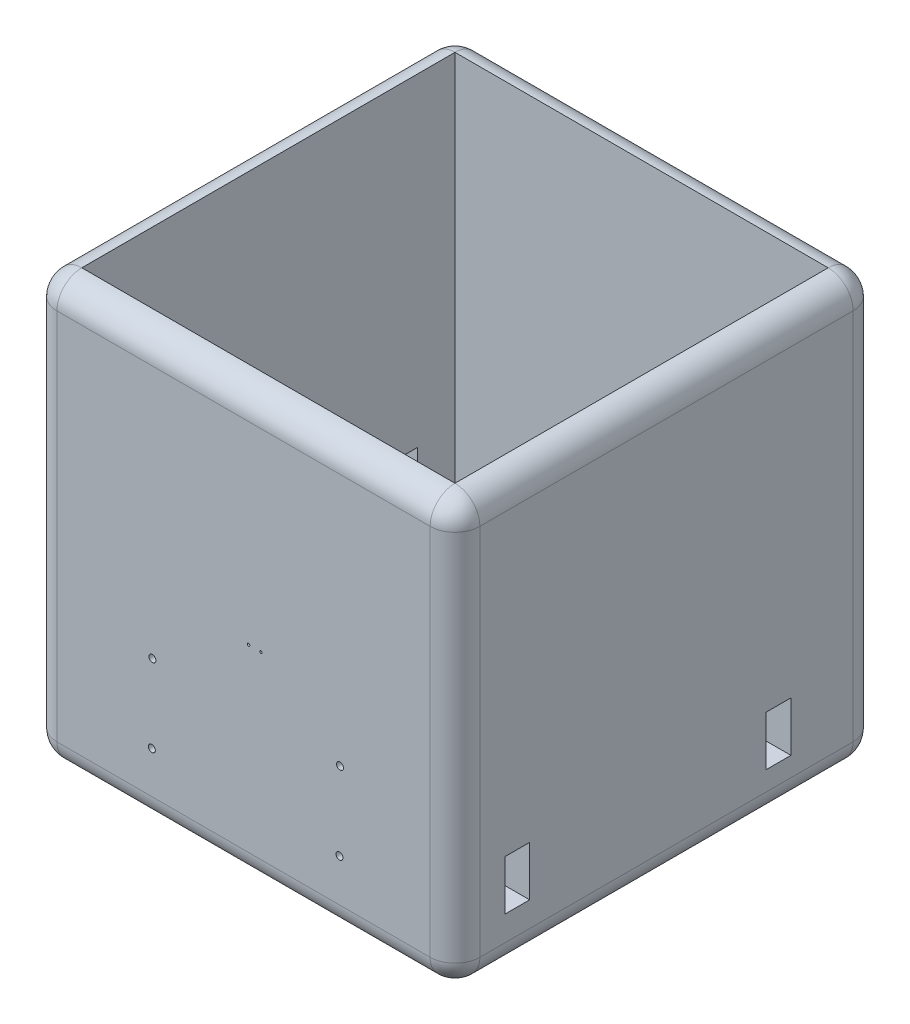
SolidWorks part; units mm, degrees
ref_plane "Front Plane" through (0, 0, 0) normal (0, 0, 1) x (1, 0, 0)
ref_plane "Top Plane" through (0, 0, 0) normal (0, 1, 0) x (1, 0, 0)
ref_plane "Right Plane" through (0, 0, 0) normal (1, 0, 0) x (0, 0, -1)
sketch "Sketch1" plane through (0, 0, 0) normal (0, 0, 1) x (1, 0, 0)
  line L5 (0, 170) -> (170, 170)
  line L6 (0, 170) -> (0, 0)
  line L7 (0, 0) -> (170, 0)
  line L8 (170, 170) -> (170, 0)
  dimension "D1" = 170
sketch "Sketch5" plane through (0, 0, 0) normal (0, 0, 1) x (1, 0, 0)
extrude "Boss-Extrude2" add sketch "Sketch1" along normal blind 170
fillet "Fillet5" radius 10 12 edges at (170, 170, 85) (85, 170, 0) (0, 85, 0) (170, 85, 0) (85, 0, 0) (170, 0, 85) (170, 85, 170) (85, 170, 170) (0, 170, 85) (0, 0, 85) (85, 0, 170) (0, 85, 170)
sketch "Sketch6" plane through (0, 170, 0) normal (0, 1, 0) x (1, 0, 0)
  line L1 (10, -10) -> (160, -10)
  line L2 (10, -10) -> (10, -160)
  line L3 (10, -160) -> (160, -160)
  line L4 (160, -10) -> (160, -160)
extrude "Cut-Extrude2" cut sketch "Sketch6" against normal blind 165
sketch "Sketch7" plane through (0, 0, 0) normal (0, -1, 0) x (-1, 0, 0)
  circle A0 centre (-49.6357, -128.1132) radius 25
extrude "Cut-Extrude3" cut sketch "Sketch7" against normal blind 5 contours A0
sketch "Sketch8" plane through (0, 0, 170) normal (0, 0, 1) x (1, 0, 0)
  circle A0 centre (87.0271, 82.2921) radius 0.5
  circle A1 centre (92.0271, 82.2592) radius 0.5
  dimension "D1" = 5
  dimension "D2" = 1
  dimension "D3" = 1
extrude "Cut-Extrude4" cut sketch "Sketch8" against normal blind 5
sketch "Sketch9" plane through (0, 0, 0) normal (0, -1, 0) x (-1, 0, 0)
  circle A0 centre (-135.3715, -22.5672) radius 7.5
extrude "Cut-Extrude5" cut sketch "Sketch9" against normal blind 5
sketch "Sketch10" plane through (0, 0, 170) normal (0, 0, 1) x (1, 0, 0)
  circle A0 centre (48.3821, 58.1964) radius 1.4
  circle A1 centre (123.7821, 58.455) radius 1.4
  circle A2 centre (48.1666, 26.7964) radius 1.4
  circle A3 centre (123.5666, 27.055) radius 1.4
  dimension "D1" = 2.8
  dimension "D2" = 75.4
  dimension "D3" = 75.4
  dimension "D4" = 31.4
  dimension "D5" = 31.4
extrude "Cut-Extrude8" cut sketch "Sketch10" against normal blind 5
sketch "Sketch14" plane through (0, 0, 0) normal (-1, 0, 0) x (0, 0, 1)
  line L0 (25, 40) -> (35, 40)
  line L1 (140, 40) -> (150, 40)
  line L2 (140, 40) -> (140, 20)
  line L3 (140, 20) -> (150, 20)
  line L4 (150, 40) -> (150, 20)
  line L5 (25, 40) -> (25, 20)
  line L6 (25, 20) -> (35, 20)
  line L7 (35, 40) -> (35, 20)
  line L8 (10, 10) -> (160, 10) construction
  line L10 (160, 10) -> (160, 160) construction
  dimension "D1" = 105
  dimension "D2" = 10
  dimension "D3" = 10
  dimension "D4" = 10
  dimension "D5" = 10
  dimension "D6" = 10
  dimension "D7" = 30
sketch "Sketch19" plane through (170, 0, 0) normal (1, 0, 0) x (0, 0, -1)
  line L0 (-45, 37.7933) -> (-35, 37.7933)
  line L1 (-150, 40) -> (-140, 40)
  line L2 (-150, 40) -> (-150, 20)
  line L3 (-150, 20) -> (-140, 20)
  line L4 (-140, 40) -> (-140, 20)
  line L5 (-45, 37.7933) -> (-45, 17.7933)
  line L6 (-45, 17.7933) -> (-35, 17.7933)
  line L7 (-35, 37.7933) -> (-35, 17.7933)
  line L8 (-160, 160) -> (-160, 10) construction
  line L9 (-160, 10) -> (-10, 10) construction
  dimension "D1" = 105
  dimension "D2" = 10
  dimension "D3" = 10
  dimension "D4" = 20
extrude "Cut-Extrude12" cut sketch "Sketch19" against normal blind 15 contours L2 L1 L4 L3 | L0 L7 L6 L5
extrude "Cut-Extrude15" cut sketch "Sketch14" against normal blind 15 contours L0 L7 L6 L5
sketch "Sketch34" plane through (0, 0, 0) normal (-1, 0, 0) x (0, 0, 1)
extrude "Cut-Extrude16" cut sketch "Sketch14<5>" against normal blind 15
sketch "Sketch14<5>" plane through (0, 0, 0) normal (-1, 0, 0) x (0, 0, 1) same geometry as "Sketch14"
